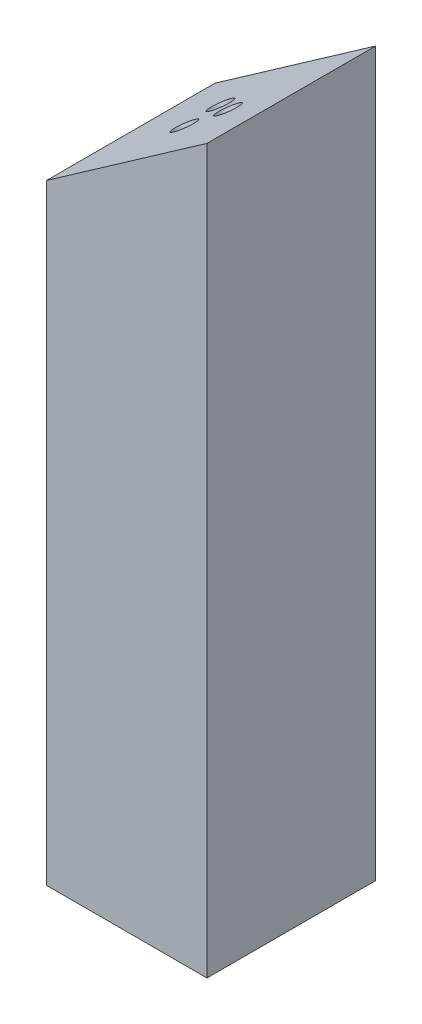
SolidWorks part; units mm, degrees
ref_plane "Front Plane" through (0, 0, 0) normal (0, 0, 1) x (1, 0, 0)
ref_plane "Top Plane" through (0, 0, 0) normal (0, 1, 0) x (1, 0, 0)
ref_plane "Right Plane" through (0, 0, 0) normal (1, 0, 0) x (0, 0, -1)
sketch "Sketch1" plane through (0, 0, 0) normal (0, 1, 0) x (1, 0, 0)
  line L0 (0, 63.205) -> (0, -68.0193) construction
  line L1 (-50, 52.5) -> (50, 52.5)
  line L2 (-50, 52.5) -> (-50, -52.5)
  line L3 (-50, -52.5) -> (50, -52.5)
  line L4 (50, 52.5) -> (50, -52.5)
  line L5 (-81.7056, 0) -> (95.5983, 0) construction
  dimension "D1" = 105
  dimension "D2" = 100
extrude "Boss-Extrude1" add sketch "Sketch1" along normal blind 350
sketch "Sketch2" plane through (0, 350, 0) normal (0, 1, 0) x (1, 0, 0)
  line L0 (50, -52.5) -> (50, 52.5) construction
  line L1 (-50, 52.5) -> (50, 52.5)
  line L2 (-50, 52.5) -> (-50, -52.5)
  line L3 (-50, -52.5) -> (50, -52.5)
  line L4 (50, 52.5) -> (50, -52.5)
  line L5 (-50, 52.5) -> (-50, -52.5) construction
  line L6 (50, 52.5) -> (-50, 52.5) construction
  line L7 (-50, -52.5) -> (50, -52.5) construction
extrude "Boss-Extrude2" add sketch "Sketch2" along normal blind 100
sketch "Sketch3" plane through (0, 0, 52.5) normal (0, 0, 1) x (1, 0, 0)
  line L0 (-50, 450) -> (50, 450)
  line L1 (50, 450) -> (-50, 379.9792)
  line L2 (-50, 379.9792) -> (-50, 450)
  line L3 (-50, 450) -> (-50, 0) construction
  line L4 (-50, 450) -> (50, 450) construction
  dimension "D1" = 35
extrude "Cut-Extrude1" cut sketch "Sketch3" against normal up to next
shell "Shell1" thickness 5 removed face at (0, 0, 0)
sketch "Sketch4" plane through (-194.9813, 278.4622, 0) normal (-0.5736, 0.8192, 0) x (0.8192, 0.5736, 0)
  line L0 (238.0283, 101.3688) -> (238.0283, -153.5481) construction
  line L1 (347.0583, 0) -> (151.3464, 0) construction
  line L2 (176.9895, -52.5) -> (299.067, -52.5) construction
  line L3 (299.067, 52.5) -> (176.9895, 52.5) construction
  line L4 (176.9895, 52.5) -> (176.9895, -52.5) construction
  line L5 (299.067, -52.5) -> (299.067, 52.5) construction
  line L6 (238.0283, 0) -> (231.5283, 11.2583) construction
  circle A0 centre (238.0283, 0) radius 13 construction
  circle A1 centre (251.0283, 0) radius 7
  circle A2 centre (231.5283, -11.2583) radius 7
  circle A3 centre (231.5283, 11.2583) radius 7
  dimension "D1" = 26
  dimension "D2" = 14
  dimension "D3" = 14
  dimension "D4" = 14
  dimension "D5" = 120
extrude "Cut-Extrude2" cut sketch "Sketch4" against normal up to next
sketch "Sketch5" plane through (-50, 0, 0) normal (-1, 0, 0) x (0, 0, 1)
  line L0 (0, 0) -> (0, 504.2263) construction
  line L1 (-35, 369.9792) -> (35, 369.9792)
  line L2 (-35, 369.9792) -> (-35, 353.9792)
  line L3 (-35, 353.9792) -> (35, 353.9792)
  line L4 (35, 369.9792) -> (35, 353.9792)
  line L5 (-52.5, 379.9792) -> (52.5, 379.9792) construction
  dimension "D1" = 16
  dimension "D2" = 70
  dimension "D3" = 10
extrude "Cut-Extrude3" cut sketch "Sketch5" against normal up to next
fillet "Fillet1" radius 8 4 edges at (-47.5, 353.9792, 35) (-47.5, 369.9792, 35) (-47.5, 353.9792, -35) (-47.5, 369.9792, -35)
ref_plane "Plane1" through (0, 450, 0) normal (0, -1, 0) x (-1, 0, 0)
ref_plane "Plane2" through (0, 400, 0) normal (0, -1, 0) x (-1, 0, 0)
ref_plane "Plane3" through (0, 340, 0) normal (0, -1, 0) x (-1, 0, 0)
